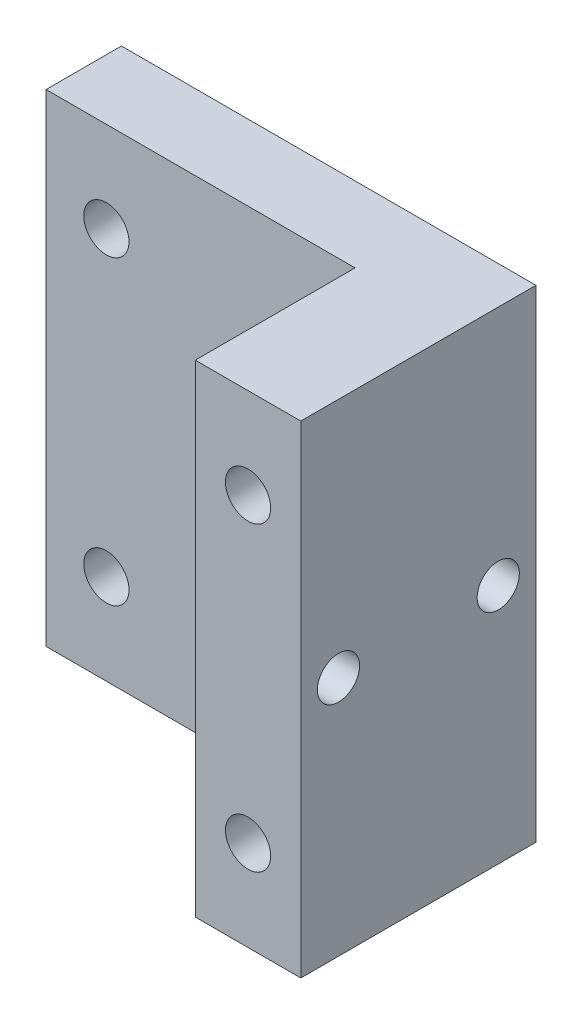
SolidWorks part; units mm, degrees
ref_plane "Front Plane" through (0, 0, 0) normal (0, 0, 1) x (1, 0, 0)
ref_plane "Top Plane" through (0, 0, 0) normal (0, 1, 0) x (1, 0, 0)
ref_plane "Right Plane" through (0, 0, 0) normal (1, 0, 0) x (0, 0, -1)
sketch "Sketch1" plane through (0, 0, 0) normal (0, 0, 1) x (1, 0, 0)
  line L1 (374.1154, -314.2464) -> (346.6154, -314.2464)
  line L2 (374.1154, -314.2464) -> (374.1154, -346.2464)
  line L3 (374.1154, -346.2464) -> (346.6154, -346.2464)
  line L4 (346.6154, -314.2464) -> (346.6154, -346.2464)
  line L8 (374.1154, -314.2464) -> (367.1154, -314.2464)
  line L9 (374.1154, -314.2464) -> (374.1154, -346.2464)
  line L10 (374.1154, -346.2464) -> (367.1154, -346.2464)
  line L11 (367.1154, -314.2464) -> (367.1154, -346.2464)
  circle A1 centre (370.6154, -340.2464) radius 1.5
  circle A2 centre (370.6154, -320.2464) radius 1.5
  circle A4 centre (350.6154, -320.2464) radius 1.5
  circle A5 centre (350.6154, -340.2464) radius 1.5
  dimension "D4" = 3
  dimension "D5" = 3
  dimension "D6" = 3
  dimension "D7" = 3
  dimension "D8" = 20
  dimension "D9" = 20
  dimension "D10" = 20
  dimension "D3" = 7
  dimension "D11" = 0
extrude "Boss-Extrude1" add sketch "Sketch1" along normal blind 5 contours L1 L11 L3 L2 A2 A1 | L11 L1 L4 L3 region at (370.6154, -330.2464, 0) region at (357.0031, -330.2464, 0)
extrude "Boss-Extrude2" add sketch "Sketch1<3>" along normal blind 15.6 contours L1 L11 L3 L2 A2 A1 region at (370.6154, -330.2464, 0)
sketch "Sketch1<3>" plane through (0, 0, 0) normal (0, 0, 1) x (1, 0, 0) same geometry as "Sketch1"
sketch "Sketch2" plane through (374.1154, 0, 0) normal (1, 0, 0) x (0, 0, -1)
  line L0 (-15.6001, -330.2464) -> (0, -330.2464) construction
  line L1 (0, -314.2464) -> (0, -346.2464) construction
  arc A0 (-12.711, -327.7769) -> (-12.711, -332.716) centre (-13.1001, -330.2464) ccw construction
  circle A1 centre (-13.1001, -330.2464) radius 1.4
  circle A2 centre (-2.5001, -330.2464) radius 1.4
  dimension "D1" = 2.8
  dimension "D2" = 2.8
extrude "Cut-Extrude1" cut sketch "Sketch2" against normal through all
sketch "Sketch3" plane through (346.6154, 0, 0) normal (-1, 0, 0) x (0, 0, 1)
  line L1 (5.4922, -331.992) -> (5.5079, -328.528)
  line L2 (5.5079, -328.528) -> (2.5157, -326.7824)
  line L3 (2.5157, -326.7824) -> (-0.4921, -328.5008)
  line L4 (-0.4921, -328.5008) -> (-0.5077, -331.9649)
  line L5 (-0.5077, -331.9649) -> (2.4844, -333.7105)
  line L6 (2.4844, -333.7105) -> (5.4922, -331.992)
  circle A0 centre (2.5001, -330.2464) radius 3 construction
  dimension "D1" = 6
